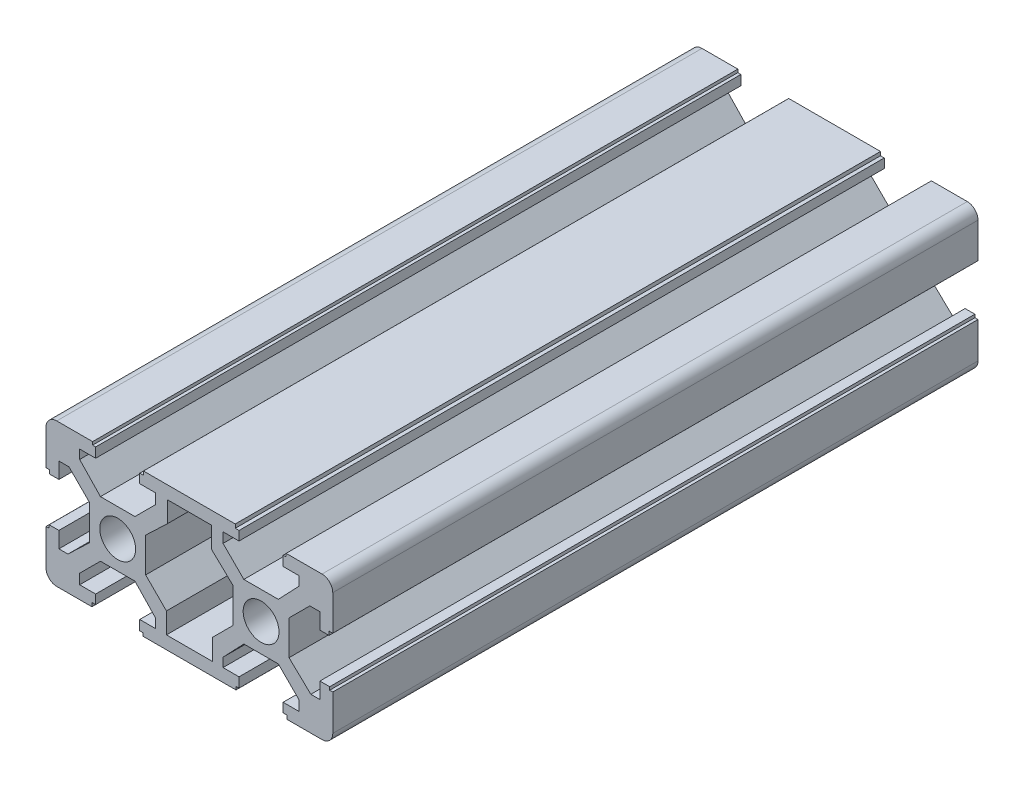
SolidWorks part; units mm, degrees
ref_plane "Front Plane" through (0, 0, 0) normal (0, 0, 1) x (1, 0, 0)
ref_plane "Top Plane" through (0, 0, 0) normal (0, 1, 0) x (1, 0, 0)
ref_plane "Right Plane" through (0, 0, 0) normal (1, 0, 0) x (0, 0, -1)
sketch "Sketch1" plane through (0, 0, 0) normal (0, 0, 1) x (1, 0, 0)
  line L0 (-3.0596, 5.3047) -> (-3.0596, 8.2)
  line L1 (-3.0596, 8.2) -> (0, 8.2)
  line L2 (-6.1, 0) -> (6.1, 0) construction
  line L4 (-1.5, 10) -> (0, 10)
  line L5 (-20, -3.4975) -> (-20, -10)
  line L6 (-18.5, -10) -> (-13.6, -10)
  line L7 (-6.1, 2.4047) -> (-3.0596, 5.3047)
  line L10 (-3.2, -5.3047) -> (-3.2, -8.2)
  line L11 (-3.2, -8.2) -> (0, -8.2)
  line L13 (-6.1, -2.4047) -> (-3.2, -5.3047)
  line L14 (-6.1, -2.4047) -> (-6.1, 2.4047)
  line L15 (-6.5025, -9.5731) -> (-6.5025, -10)
  line L16 (-6.925, -9.5658) -> (-6.5025, -9.5731)
  line L17 (-6.925, -8.2) -> (-6.925, -9.5658)
  line L18 (-4.6953, -8.2) -> (-6.925, -8.2)
  line L19 (-4.6953, -8.2) -> (-4.6953, -6.9404)
  line L20 (-6.5025, -10) -> (-1.6025, -10)
  line L21 (0, -10) -> (-1.6025, -10)
  line L22 (-7.5953, -3.9) -> (-4.6953, -6.9404)
  line L23 (-13.6, -9.4791) -> (-13.6, -10)
  line L24 (-13.075, -9.4791) -> (-13.6, -9.4791)
  line L25 (-13.075, -8.2) -> (-13.075, -9.4791)
  line L26 (-15.3047, -8.2) -> (-13.075, -8.2)
  line L27 (-15.3047, -8.2) -> (-15.3047, -6.8)
  line L28 (-12.4047, -3.9) -> (-15.3047, -6.8)
  line L29 (-12.4047, -3.9) -> (-7.5953, -3.9)
  line L30 (-19.5731, -3.4975) -> (-20, -3.4975)
  line L31 (-19.5658, -3.075) -> (-19.5731, -3.4975)
  line L32 (-18.2, -3.075) -> (-19.5658, -3.075)
  line L33 (-18.2, -5.3047) -> (-18.2, -3.075)
  line L34 (-18.2, -5.3047) -> (-16.9404, -5.3047)
  line L35 (0, 8.2) -> (3.0596, 8.2)
  line L36 (-1.5, 10) -> (-6.4, 10)
  line L37 (-13.9, -2.4047) -> (-16.9404, -5.3047)
  line L38 (-19.4791, 3.6) -> (-20, 3.6)
  line L39 (-19.4791, 3.075) -> (-19.4791, 3.6)
  line L40 (-18.2, 3.075) -> (-19.4791, 3.075)
  line L41 (-18.2, 5.3047) -> (-18.2, 3.075)
  line L42 (-18.2, 5.3047) -> (-16.8, 5.3047)
  line L43 (-13.9, 2.4047) -> (-16.8, 5.3047)
  line L44 (-13.9, 2.4047) -> (-13.9, -2.4047)
  line L45 (-12.4047, 3.9) -> (-15.3047, 6.9404)
  line L47 (-15.3047, 8.2) -> (-15.3047, 6.9404)
  line L48 (-7.5953, 3.9) -> (-4.6953, 6.8)
  line L49 (-4.6953, 8.2) -> (-4.6953, 6.8)
  line L50 (-20, 3.6) -> (-20, 10)
  line L51 (-13.4975, 10) -> (-20, 10)
  line L52 (-18.5, -10) -> (-1.6025, -10) construction
  line L53 (20, 8.5035) -> (20, 10) construction
  line L54 (3.0596, 5.3047) -> (3.0596, 8.2)
  line L55 (-20, -10) -> (0, 10) construction
  line L56 (-20, 10) -> (0, -10) construction
  line L60 (-10, 0) -> (-13.9, 0) construction
  line L61 (-10, 0) -> (-10, 3.9) construction
  line L62 (-10, 0) -> (-6.1, 0) construction
  line L63 (-13, 6.4) -> (-7, 6.4) construction
  line L64 (-13, 6.4) -> (-13, 4.9) construction
  line L65 (-13, 4.9) -> (-7, 4.9) construction
  line L66 (-6.4, 9.4791) -> (-6.4, 10)
  line L67 (-6.925, 9.4791) -> (-6.4, 9.4791)
  line L68 (-6.925, 8.2) -> (-6.925, 9.4791)
  line L69 (-10, 0) -> (-10, -3.9) construction
  line L70 (-4.6953, 8.2) -> (-6.925, 8.2)
  line L76 (-7, 6.4) -> (-7, 4.9) construction
  line L77 (-13, 6.4) -> (-7, 4.9) construction
  line L78 (-13, 4.9) -> (-7, 6.4) construction
  line L86 (-7.5953, 3.9) -> (-12.4047, 3.9)
  line L88 (-15.3047, 8.2) -> (-13.075, 8.2)
  line L89 (-13.075, 8.2) -> (-13.075, 9.5658)
  line L90 (-13.075, 9.5658) -> (-13.4975, 9.5731)
  line L91 (-13.4975, 9.5731) -> (-13.4975, 10)
  line L106 (0, -10) -> (1.6025, -10)
  line L107 (0, 10) -> (1.5, 10)
  line L108 (18.5, -10) -> (20, -10)
  line L109 (20, -8.3975) -> (20, -10)
  line L112 (18.3975, 10) -> (20, 10)
  line L113 (20, 8.5035) -> (20, 10)
  line L114 (-20, -3.4975) -> (-20, 3.6) construction
  line L115 (-18.5, -10) -> (-20, -10)
  line L132 (1.6025, -10) -> (18.5, -10) construction
  line L133 (0, -8.2) -> (3.2, -8.2)
  line L134 (3.2, -5.3047) -> (3.2, -8.2)
  line L137 (13, 4.9) -> (7, 6.4) construction
  line L138 (13, 6.4) -> (7, 4.9) construction
  line L139 (7, 6.4) -> (7, 4.9) construction
  line L140 (10, 0) -> (10, -3.9) construction
  line L141 (13, 4.9) -> (7, 4.9) construction
  line L142 (13, 6.4) -> (13, 4.9) construction
  line L143 (13, 6.4) -> (7, 6.4) construction
  line L144 (10, 0) -> (6.1, 0) construction
  line L145 (10, 0) -> (10, 3.9) construction
  line L146 (10, 0) -> (13.9, 0) construction
  line L147 (20, 10) -> (0, -10) construction
  line L148 (20, -10) -> (0, 10) construction
  line L149 (20, -8.3975) -> (20, 8.5) construction
  line L150 (13.4975, 9.5731) -> (13.4975, 10)
  line L151 (13.075, 9.5658) -> (13.4975, 9.5731)
  line L152 (13.075, 8.2) -> (13.075, 9.5658)
  line L153 (15.3047, 8.2) -> (13.075, 8.2)
  line L154 (7.5953, 3.9) -> (12.4047, 3.9)
  line L155 (4.6953, 8.2) -> (6.925, 8.2)
  line L156 (6.925, 8.2) -> (6.925, 9.4791)
  line L157 (6.925, 9.4791) -> (6.4, 9.4791)
  line L158 (6.4, 9.4791) -> (6.4, 10)
  line L159 (20, 8.5) -> (20, 3.6)
  line L160 (13.4975, 10) -> (18.3975, 10)
  line L161 (4.6953, 8.2) -> (4.6953, 6.8)
  line L162 (7.5953, 3.9) -> (4.6953, 6.8)
  line L163 (15.3047, 8.2) -> (15.3047, 6.9404)
  line L164 (12.4047, 3.9) -> (15.3047, 6.9404)
  line L165 (13.9, 2.4047) -> (13.9, -2.4047)
  line L166 (13.9, 2.4047) -> (16.8, 5.3047)
  line L167 (18.2, 5.3047) -> (16.8, 5.3047)
  line L168 (18.2, 5.3047) -> (18.2, 3.075)
  line L169 (18.2, 3.075) -> (19.4791, 3.075)
  line L170 (19.4791, 3.075) -> (19.4791, 3.6)
  line L171 (19.4791, 3.6) -> (20, 3.6)
  line L172 (13.9, -2.4047) -> (16.9404, -5.3047)
  line L173 (1.5, 10) -> (6.4, 10)
  line L174 (18.2, -5.3047) -> (16.9404, -5.3047)
  line L175 (18.2, -5.3047) -> (18.2, -3.075)
  line L176 (18.2, -3.075) -> (19.5658, -3.075)
  line L177 (19.5658, -3.075) -> (19.5731, -3.4975)
  line L178 (19.5731, -3.4975) -> (20, -3.4975)
  line L179 (12.4047, -3.9) -> (7.5953, -3.9)
  line L180 (12.4047, -3.9) -> (15.3047, -6.8)
  line L181 (15.3047, -8.2) -> (15.3047, -6.8)
  line L182 (15.3047, -8.2) -> (13.075, -8.2)
  line L183 (13.075, -8.2) -> (13.075, -9.4791)
  line L184 (13.075, -9.4791) -> (13.6, -9.4791)
  line L185 (13.6, -9.4791) -> (13.6, -10)
  line L186 (7.5953, -3.9) -> (4.6953, -6.9404)
  line L187 (6.5025, -10) -> (1.6025, -10)
  line L188 (4.6953, -8.2) -> (4.6953, -6.9404)
  line L189 (4.6953, -8.2) -> (6.925, -8.2)
  line L190 (6.925, -8.2) -> (6.925, -9.5658)
  line L191 (6.925, -9.5658) -> (6.5025, -9.5731)
  line L192 (6.5025, -9.5731) -> (6.5025, -10)
  line L193 (6.1, -2.4047) -> (6.1, 2.4047)
  line L194 (6.1, -2.4047) -> (3.2, -5.3047)
  line L195 (6.1, 2.4047) -> (3.0596, 5.3047)
  line L196 (18.5, -10) -> (13.6, -10)
  line L197 (20, -3.4975) -> (20, -8.3975)
  line L198 (0, 10) -> (0, -10) construction
  line L199 (20, 8.5035) -> (20, 8.5)
  circle A0 centre (-10, 0) radius 2.5
  circle A1 centre (10, 0) radius 2.5
  point P57 (-10, 0)
  point P63 (-10, 0)
  dimension "D1" = 6
  dimension "D2" = 1.5
  dimension "D3" = 3.075
  dimension "D4" = 3.075
  dimension "D5" = 3.075
  dimension "D6" = 20
  dimension "D7" = 20
  dimension "D8" = 40
extrude "Boss-Extrude1" add sketch "Sketch1" against normal blind 90
fillet "Fillet1" radius 1.5 4 edges at (-20, -10, -45) (-20, 10, -45) (20, -10, -45) (20, 10, -45)
